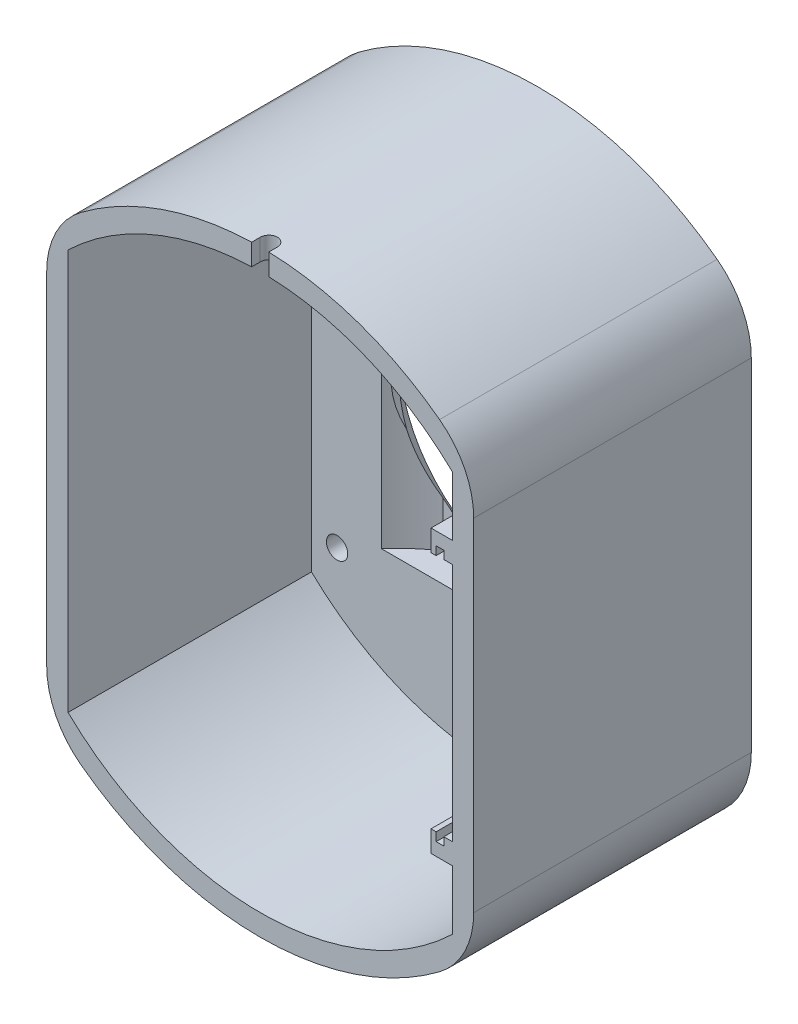
SolidWorks part; units mm, degrees
ref_plane "Спереди" through (0, 0, 0) normal (0, 0, 1) x (1, 0, 0)
ref_plane "Сверху" through (0, 0, 0) normal (0, 1, 0) x (1, 0, 0)
ref_plane "Справа" through (0, 0, 0) normal (1, 0, 0) x (0, 0, -1)
sketch "Эскиз1" plane through (0, 0, 0) normal (0, 0, 1) x (1, 0, 0)
  line L1 (45, -46.9042) -> (45, 46.9042)
  line L2 (0, 0) -> (0, -65) construction
  line L3 (50, -48.9898) -> (50, 48.9898)
  line L4 (-50, -48.9898) -> (-50, 48.9898)
  line L5 (-45, -46.9042) -> (-45, 46.9042)
  line L6 (-29.0575, -58.1435) -> (-29.0575, -34.0575)
  line L7 (-34.0575, -29.0575) -> (-45, -29.0575)
  line L8 (34.0575, -29.0575) -> (45, -29.0575)
  line L9 (29.0575, -58.1435) -> (29.0575, -34.0575)
  line L10 (34.0575, 29.0575) -> (45, 29.0575)
  line L11 (-39, -39) -> (39, 39) construction
  line L12 (-39, 39) -> (39, -39) construction
  line L13 (29.0575, 58.1435) -> (29.0575, 34.0575)
  line L14 (-34.0575, 29.0575) -> (-45, 29.0575)
  line L15 (-29.0575, 58.1435) -> (-29.0575, 34.0575)
  line L16 (-0.1, 27.5) -> (0.1, 27.5)
  line L17 (-27.5, -27.5) -> (27.5, -27.5) construction
  line L18 (-27.5, -27.5) -> (-27.5, 27.5) construction
  line L19 (-27.5, 27.5) -> (27.5, 27.5) construction
  line L20 (27.5, -27.5) -> (27.5, 27.5) construction
  line L21 (-27.5, -27.5) -> (27.5, 27.5) construction
  line L22 (-27.5, 27.5) -> (27.5, -27.5) construction
  line L23 (-27.5, 0.1) -> (-27.5, -0.1)
  line L24 (-0.1, -27.5) -> (0.1, -27.5)
  line L25 (27.5, 0.1) -> (27.5, -0.1)
  line L26 (-27.5, 27.5) -> (27.5, -27.5) construction
  line L27 (-27.5, -27.5) -> (27.5, 27.5) construction
  arc A0 (-45, -46.9042) -> (45, -46.9042) centre (0, 0) ccw
  arc A1 (50, 48.9898) -> (-50, 48.9898) centre (0, 0) ccw
  arc A2 (45, 46.9042) -> (-45, 46.9042) centre (0, 0) ccw
  circle A3 centre (0, 0) radius 65 construction
  circle A4 centre (0, 0) radius 70 construction
  arc A5 (-50, -48.9898) -> (50, -48.9898) centre (0, 0) ccw
  circle A6 centre (-39, -39) radius 2.5
  arc A7 (-29.0575, -34.0575) -> (-34.0575, -29.0575) centre (-34.0575, -34.0575) ccw
  circle A8 centre (39, -39) radius 2.5
  arc A9 (29.0575, -34.0575) -> (34.0575, -29.0575) centre (34.0575, -34.0575) cw
  circle A10 centre (39, 39) radius 2.5
  arc A11 (29.0575, 34.0575) -> (34.0575, 29.0575) centre (34.0575, 34.0575) ccw
  circle A12 centre (-39, 39) radius 2.5
  arc A13 (-29.0575, 34.0575) -> (-34.0575, 29.0575) centre (-34.0575, 34.0575) cw
  arc A14 (-27.5, -0.1) -> (-0.1, -27.5) centre (-0.1, -0.1) ccw
  arc A15 (-0.1, 27.5) -> (-27.5, 0.1) centre (-0.1, 0.1) ccw
  arc A16 (0.1, 27.5) -> (27.5, 0.1) centre (0.1, 0.1) cw
  arc A17 (0.1, -27.5) -> (27.5, -0.1) centre (0.1, -0.1) ccw
  point P4 (66.9413, 20.466)
  point P14 (65, 0)
  point P26 (-29.0575, -29.0575)
  dimension "D2" = 140
  dimension "D6" = 5
  dimension "D7" = 5
  dimension "D11" = 27.4
  dimension "D3" = 5
  dimension "D4" = 78
  dimension "D5" = 78
  dimension "D8" = 55
  dimension "D9" = 55
  dimension "D10" = 100
  dimension "D1" = 5
extrude "Extrude" add sketch "Эскиз1" along normal blind 65 contours L4 A5 L3 A1 A2 L1 A0 L5 region at (0, -68.2795, 0)
extrude "Boss-Extrude1" add sketch "Эскиз1<3>" along normal blind 8 contours L6 A7 L7 L5 A0 A6 | A9 L9 A0 L1 L8 A8 | L13 A11 L10 L1 A2 A10 | A15 A13 L15 A2 L5 L14 A12 | A15 A13 L14 L5 L7 A7 A14 L23 | A17 L24 A14 A7 L6 A0 L9 A9 | A17 A9 L8 L1 L10 A11 A16 L25 | L16 A16 A11 L13 A2 L15 A13 A15 region at (36.3642, -41.6012, 0) region at (39.5287, -27.4763, 0) region at (36.3642, 41.6012, 0) region at (-36.3642, -41.6012, 0) region at (-36.3642, 41.6012, 0)
sketch "Эскиз1<3>" plane through (0, 0, 0) normal (0, 0, 1) x (1, 0, 0) same geometry as "Эскиз1"
fillet "Fillet1" radius 20 4 edges at (50, -48.9898, 32.5) (-50, -48.9898, 32.5) (-50, 48.9898, 32.5) (50, 48.9898, 32.5)
chamfer "Chamfer3" distance 5 angle 45 8 edges at (27.5, 0, 0) (19.4747, 19.4747, 0) (19.4747, -19.4747, 0) (0, 27.5, 0) (0, -27.5, 0) (-19.4747, 19.4747, 0) (-19.4747, -19.4747, 0) (-27.5, 0, 0)
sketch "Sketch3" plane through (0, 0, 65) normal (0, 0, 1) x (1, 0, 0)
  line L0 (0, 0) -> (45, 0) construction
  line L1 (41.2, -28) -> (43, -28.1045)
  line L2 (45, -46.9042) -> (45, 46.9042) construction
  line L3 (45, 33) -> (40, 33)
  line L4 (40, 33) -> (40, 28)
  line L5 (40, 28) -> (41.2, 28)
  line L6 (41.2, 28) -> (41.2, 30)
  line L7 (41.2, 30) -> (43, 30)
  line L8 (43, 30) -> (43, 28.1045)
  line L9 (43, 28.1045) -> (45, 28.1045)
  line L10 (45, 28.1045) -> (45, 33)
  line L11 (43, -28.1045) -> (45, -28.1045)
  line L12 (43, -30) -> (43, -28.1045)
  line L13 (41.2, -30) -> (43, -30)
  line L14 (41.2, -28) -> (41.2, -30)
  line L15 (40, -28) -> (41.2, -28)
  line L16 (40, -33) -> (40, -28)
  line L17 (45, -33) -> (40, -33)
  line L18 (45, -28.1045) -> (45, -33)
  line L19 (41.2, 28) -> (43, 28.1045)
  point P7 (42.1, 30)
  dimension "D1" = 1.8
  dimension "D2" = 5
  dimension "D3" = 3
  dimension "D4" = 30
  dimension "D5" = 5
  dimension "D6" = 2
extrude "Boss-Extrude3" add sketch "Sketch3" against normal blind 10 contours L18 L12 L13 L14 L16 L17 | L16 L14 L15 | L10 L3 L4 L6 L7 L8 | L5 L6 L4 region at (42.5532, -30.779, 65) region at (42.5532, 30.779, 65)
extrude "Boss-Extrude4" add sketch "Sketch3<2>" along normal blind 10 from offset 45 contours L18 L12 L13 L14 L16 L17 | L16 L14 L15 | L10 L3 L4 L6 L7 L8 | L5 L6 L4 region at (42.5532, -30.779, 65) region at (42.5532, 30.779, 65) offset against normal yes
sketch "Sketch3<2>" plane through (0, 0, 65) normal (0, 0, 1) x (1, 0, 0) same geometry as "Sketch3"
sketch "Sketch5" plane through (0, 0, 0) normal (0, 1, 0) x (1, 0, 0)
  line L0 (0, 0) -> (0, -65) construction
  line L1 (-42, -65) -> (42, -65) construction
  line L2 (-2, -63) -> (-2, -65)
  line L3 (-2, -65) -> (2, -65)
  line L4 (2, -65) -> (2, -63)
  arc A0 (2, -63) -> (-2, -63) centre (0, -63) ccw
  circle A1 centre (5, -55) radius 1.1
  circle A2 centre (-5, -55) radius 1.1
  dimension "D1" = 4
  dimension "D2" = 2
  dimension "D3" = 2.2
  dimension "D4" = 5
  dimension "D5" = 10
extrude "Cut-Extrude2" cut sketch "Sketch5" along normal through all contours A0 L0 L3 L4 | L0 A0 L2 L3 region at (0.9335, 0, 63.1867) region at (-0.9335, 0, 63.1867)
extrude "Cut-Extrude3" cut sketch "Sketch5<4>" along normal blind 68 contours A2 | A1
sketch "Sketch5<4>" plane through (0, 0, 0) normal (0, 1, 0) x (1, 0, 0) same geometry as "Sketch5"
sketch "Sketch6" plane through (0, 0, 0) normal (0, 1, 0) x (1, 0, 0)
  line L0 (0, 0) -> (0, -65) construction
  line L1 (-45, -65) -> (45, -65) construction
  line L2 (-21, -1.25) -> (21, -1.25)
  line L3 (-45, -8) -> (45, -8) construction
  line L4 (28.5887, -8) -> (-0.1, -8)
  line L5 (-28.5887, -8) -> (0.1, -8)
  line L6 (42, 0) -> (-42, 0) construction
  arc A0 (21, -1.25) -> (28.5887, -8) centre (0, -32.5) cw
  arc A1 (-21, -1.25) -> (-28.5887, -8) centre (0, -32.5) ccw
  point P7 (0, -32.5)
  point P17 (0, -1.25)
  dimension "D1" = 21
  dimension "D2" = 1.25
extrude "Cut-Extrude4" cut sketch "Sketch6" against normal mid plane 68 contours L2 L0 L4 A0 | L0 L2 A1 L5 region at (12.6642, 0, 4.7934) region at (-12.6642, 0, 4.7934)
chamfer "Chamfer4" distance 2 angle 45 4 edges at (41.5, 39, 0) (-36.5, 39, 0) (-36.5, -39, 0) (41.5, -39, 0)
